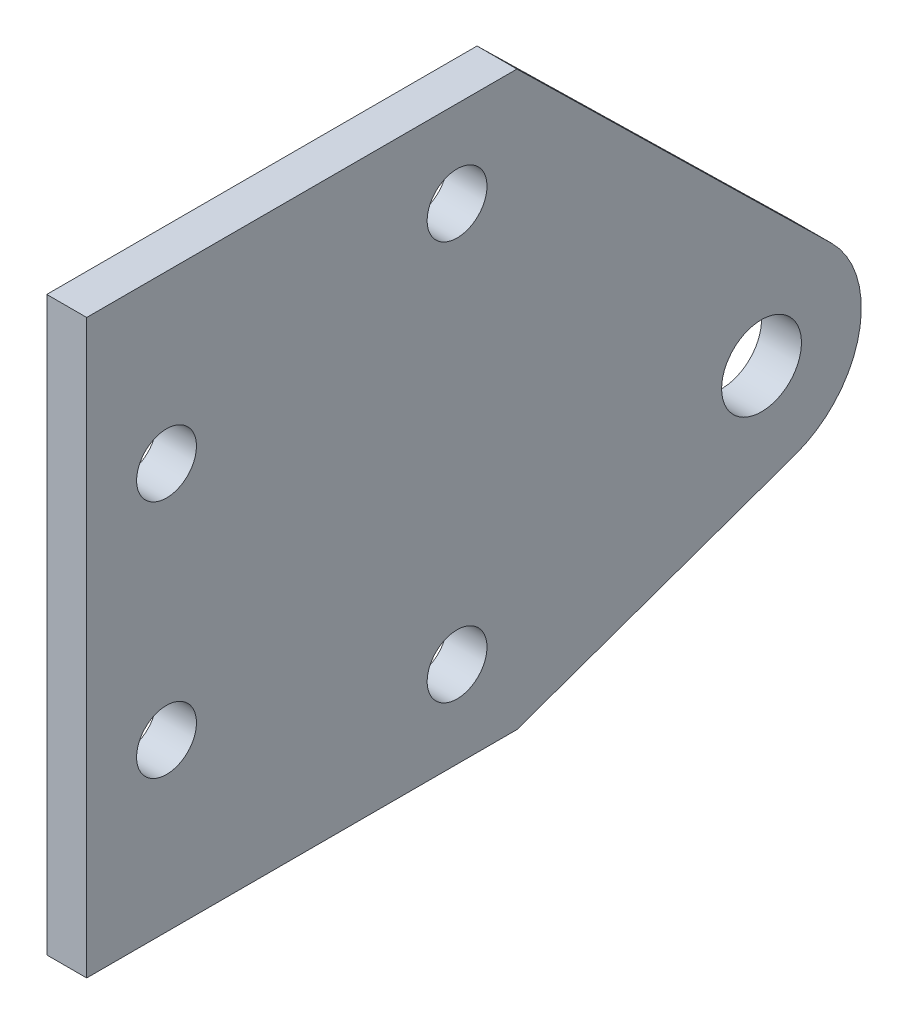
SolidWorks part; units mm, degrees
ref_plane "Front Plane" through (0, 0, 0) normal (0, 0, 1) x (1, 0, 0)
ref_plane "Top Plane" through (0, 0, 0) normal (0, 1, 0) x (1, 0, 0)
ref_plane "Right Plane" through (0, 0, 0) normal (1, 0, 0) x (0, 0, -1)
sketch "Sketch1" plane through (-25.4, 0, 0) normal (-1, 0, 0) x (0, 0, 1)
  line L6 (-88.4975, 379.3607) -> (-113.504, 354.8689) construction
  line L9 (-88.4975, 379.3607) -> (-113.504, 354.8689)
  line L24 (-103.0725, 379.3607) -> (-103.0725, 365.0857)
  line L25 (-103.0725, 379.3607) -> (-103.0725, 365.0857)
  line L26 (-54.275, 379.3607) -> (-103.0725, 379.3607)
  line L27 (-103.0725, 365.0857) -> (-113.504, 354.8689)
  line L28 (-110.6082, 341.719) -> (-88.4975, 333.8607)
  line L29 (-88.4975, 333.8607) -> (-54.275, 333.8607)
  line L30 (-54.275, 333.8607) -> (-54.275, 379.3607)
  line L31 (-54.275, 379.3607) -> (-103.0725, 379.3607)
  line L32 (-103.0725, 365.0857) -> (-113.504, 354.8689)
  line L33 (-110.6082, 341.719) -> (-88.4975, 333.8607)
  line L34 (-88.4975, 333.8607) -> (-54.275, 333.8607)
  line L35 (-54.275, 333.8607) -> (-54.275, 379.3607)
  circle A1 centre (-83.735, 372.4857) radius 2.3813 construction
  circle A2 centre (-83.735, 340.7357) radius 2.3813 construction
  circle A3 centre (-60.625, 366.1357) radius 2.3813 construction
  circle A4 centre (-60.625, 347.0857) radius 2.3813 construction
  circle A6 centre (-83.735, 372.4857) radius 2.3813
  circle A7 centre (-83.735, 340.7357) radius 2.3813
  circle A8 centre (-60.625, 366.1357) radius 2.3813
  circle A9 centre (-60.625, 347.0857) radius 2.3813
  circle A13 centre (-107.95, 349.1982) radius 3.175
  circle A14 centre (-107.95, 349.1982) radius 3.175
  arc A15 (-113.504, 354.8689) -> (-110.6082, 341.719) centre (-107.95, 349.1982) ccw
  arc A16 (-113.504, 354.8689) -> (-110.6082, 341.719) centre (-107.95, 349.1982) ccw
  circle M7 centre (-60.625, 347.0857) radius 3.2639
  circle M8 centre (-83.735, 340.7357) radius 3.2639
  line M9 (-54.275, 379.3607) -> (-88.4975, 379.3607)
  line M10 (-88.4975, 379.3607) -> (-102.0374, 362.628)
  arc M11 (-102.0374, 362.628) -> (-102.1959, 351.8452) centre (-95.25, 357.1357) ccw
  line M12 (-102.1959, 351.8452) -> (-88.4975, 333.8607)
  line M13 (-88.4975, 333.8607) -> (-54.275, 333.8607)
  line M14 (-54.275, 333.8607) -> (-54.275, 379.3607)
  circle M15 centre (-95.25, 357.1357) radius 3.9687
  circle M16 centre (-83.735, 372.4857) radius 3.2639
  circle M17 centre (-60.625, 366.1357) radius 3.2639
  dimension "D1" = 0
  dimension "D2" = 0
extrude "Boss-Extrude1" add sketch "Sketch1" along normal blind 3.175 contours L9 A16 L33 A14 M12 M11 M10 | M14 M9 M10 M11 M12 M13 M8 M15 M17 M16 M7 | M15 | A8 M17 | A6 M16 | A9 M7 | A7 M8 region at (-25.4, 349.3499, -104.1542) region at (-25.4, 356.6452, -75.7783) region at (-25.4, 347.0857, -63.7966) region at (-25.4, 340.7357, -86.9066) region at (-25.4, 357.1357, -95.25) region at (-25.4, 372.4857, -86.9066) region at (-25.4, 366.1357, -63.7966)
